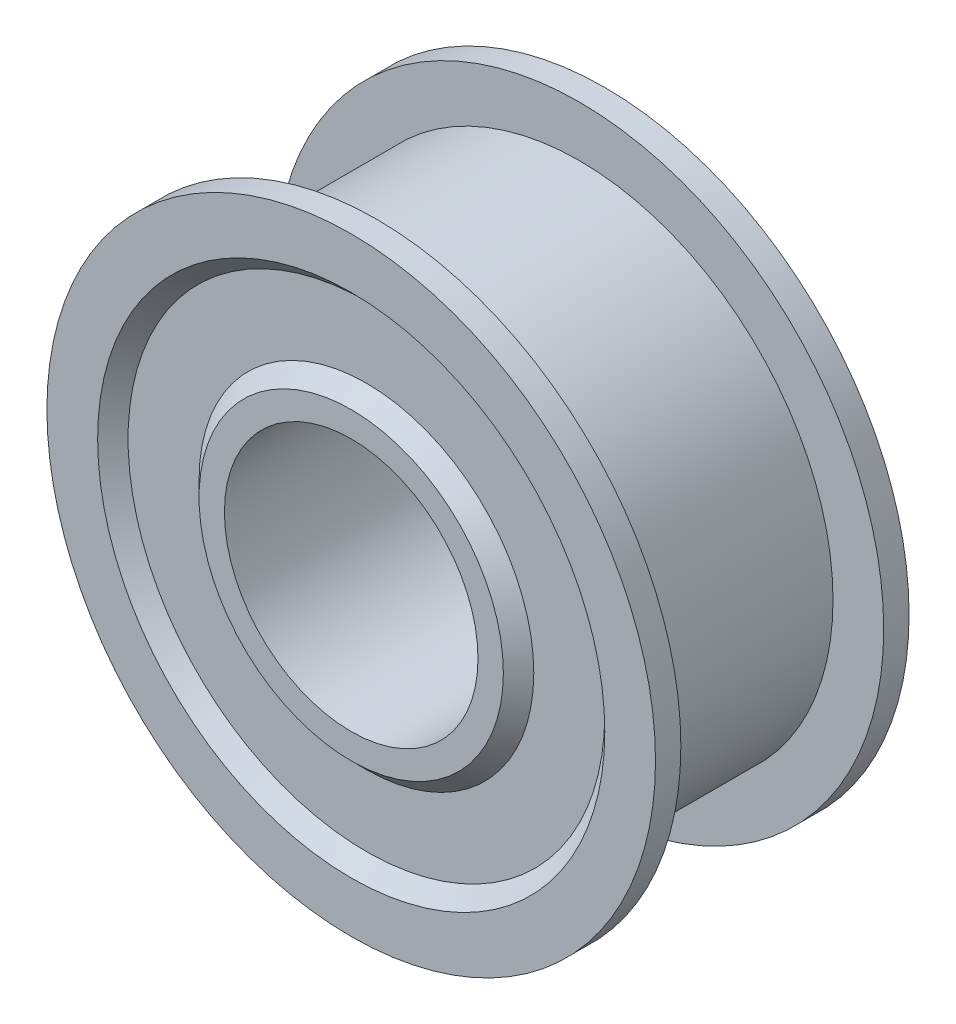
SolidWorks part; units mm, degrees
ref_plane "Alzado" through (0, 0, 0) normal (0, 0, 1) x (1, 0, 0)
ref_plane "Planta" through (0, 0, 0) normal (0, 1, 0) x (1, 0, 0)
ref_plane "Vista lateral" through (0, 0, 0) normal (1, 0, 0) x (0, 0, -1)
sketch "Croquis1" plane through (0, 0, 0) normal (0, 0, 1) x (1, 0, 0)
  circle A0 centre (0, 0) radius 12.5
  circle A1 centre (0, 0) radius 30
  dimension "D1" = 25
  dimension "D2" = 60
extrude "Saliente-Extruir1" add sketch "Croquis1" along normal blind 25
sketch "Croquis3" plane through (0, 0, 0) normal (1, 0, 0) x (0, 0, -1)
  line L0 (0, 30) -> (-25, 30) construction
  line L1 (-2.5, 25) -> (-22.5, 25)
  line L2 (-2.5, 25) -> (-2.5, 35)
  line L3 (-2.5, 35) -> (-22.5, 35)
  line L4 (-22.5, 25) -> (-22.5, 35)
  line L5 (-2.5, 25) -> (-22.5, 35) construction
  line L6 (-2.5, 35) -> (-22.5, 25) construction
  point P0 (-12.5, 30)
  dimension "D1" = 20
ref_axis "Eje1" through (0, 0, 25) along (0, 0, -1)
revolve "Cortar-Revolución1" cut sketch "Croquis3" angle 360 about axis through (0, 0, 25) along (0, 0, -1)
sketch "Croquis4" plane through (0, 0, 25) normal (0, 0, 1) x (1, 0, 0)
  circle A0 centre (0, 0) radius 15
  circle A3 centre (0, 0) radius 25
ref_plane "Plano1" through (0, 0, 12.5) normal (0, 0, 1) x (1, 0, 0)
extrude "Cortar-Extruir1" cut sketch "Croquis4" against normal blind 1.5
chamfer "Chaflán2" distance 1.5 angle 45 2 edges at (25, 0, 23.5) (15, 0, 23.5)
mirror "Simetría2" about plane through (0, 0, 12.5) normal (0, 0, 1) of "Chaflán2", "Cortar-Extruir1"
